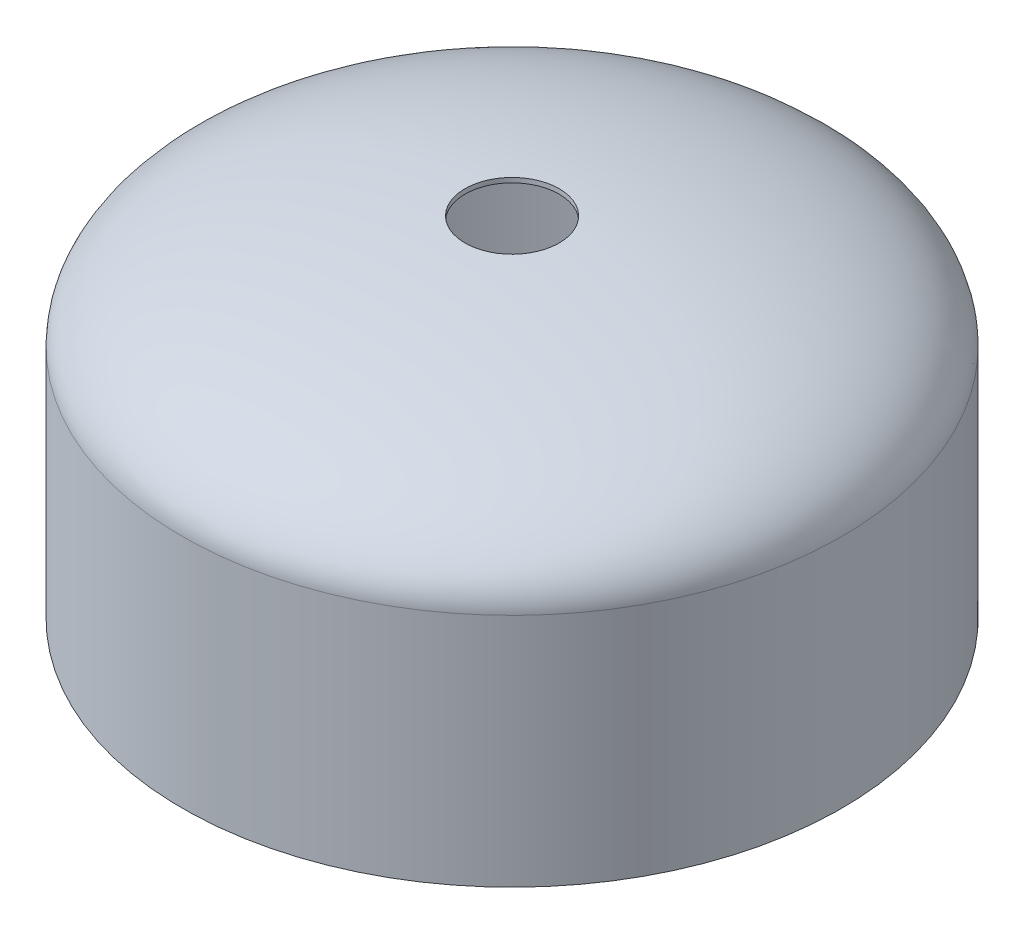
SolidWorks part; units mm, degrees
ref_plane "Front Plane" through (0, 0, 0) normal (0, 0, 1) x (1, 0, 0)
ref_plane "Top Plane" through (0, 0, 0) normal (0, 1, 0) x (1, 0, 0)
ref_plane "Right Plane" through (0, 0, 0) normal (1, 0, 0) x (0, 0, -1)
sketch "Sketch1" plane through (0, 0, 0) normal (0, 0, 1) x (1, 0, 0)
  line L0 (175.26, -127) -> (175.26, 0)
  line L1 (175.26, -127) -> (177.8, -127)
  line L2 (177.8, -127) -> (177.8, 0)
  line L3 (55, 0) -> (-55, 0) construction
  line L4 (25.4, 60.96) -> (25.4, 58.42)
  line L5 (0, -55) -> (0, 55) construction
  ellipse E0 centre (0, 0) end of major axis (177.8, 0) minor radius 61.5917 (177.8, 0) -> (25.4, 60.96) ccw
  ellipse E1 centre (0, 0) end of major axis (175.26, 0) minor radius 59.0434 (175.26, 0) -> (25.4, 58.42) ccw
  dimension "D1" = 177.8
  dimension "D2" = 2.54
  dimension "D3" = 127
  dimension "D4" = 2.54
  dimension "D5" = 25.4
  dimension "D6" = 58.42
ref_axis "Axis1" through (0, -109.728, 0) along (0, 1, 0)
revolve "Revolve1" add sketch "Sketch1" angle 360 about axis through (0, -109.728, 0) along (0, 1, 0)
